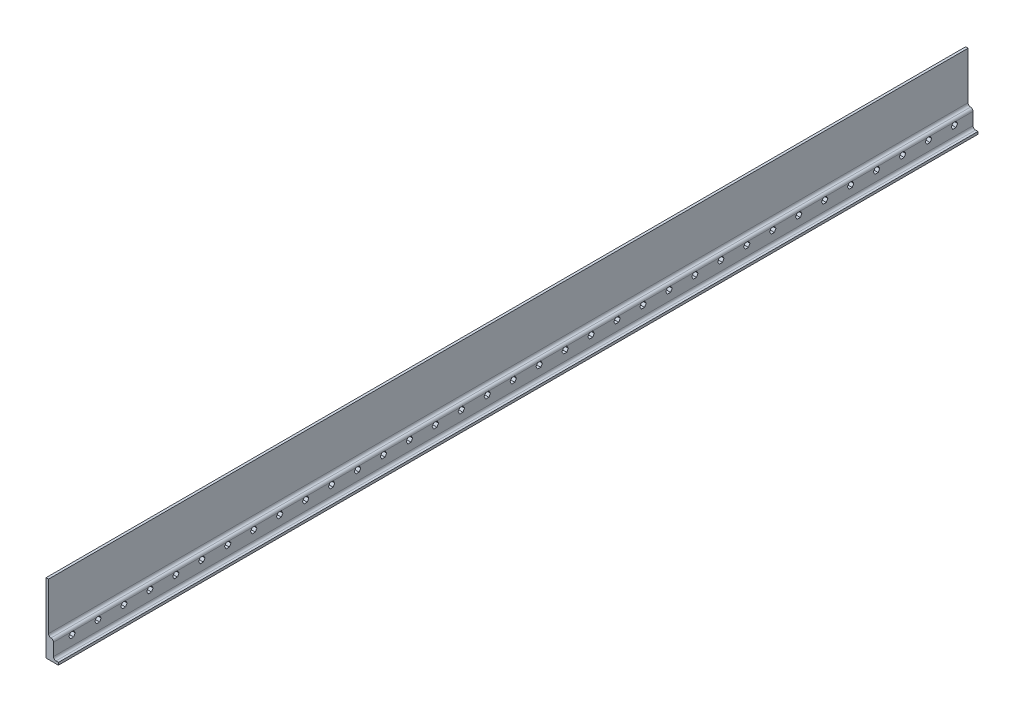
SolidWorks part; units mm, degrees
material "AISI 4340 Steel, annealed"
ref_plane "Front Plane" through (0, 0, 0) normal (0, 0, 1) x (1, 0, 0)
ref_plane "Top Plane" through (0, 0, 0) normal (0, 1, 0) x (1, 0, 0)
ref_plane "Right Plane" through (0, 0, 0) normal (1, 0, 0) x (0, 0, -1)
sketch "Sketch2" plane through (0, 0, 0) normal (0, 0, 1) x (1, 0, 0)
  line L0 (-12.5, 20) -> (12.5, -20) construction
  line L5 (-12.5, -20) -> (12.5, 20) construction
  line L6 (-12.5, 20) -> (-12.5, -20)
  line L7 (-12.5, -20) -> (12.5, -20)
  line L8 (12.5, -20) -> (12.5, -15)
  line L9 (12.5, -15) -> (2.5, -15)
  line L10 (2.5, -15) -> (2.5, 20)
  line L11 (2.5, 20) -> (-12.5, 20)
  point P4 (0, 0)
  point P6 (0, 0)
  dimension "D1" = 25
  dimension "D2" = 40
  dimension "D3" = 15
  dimension "D4" = 5
extrude "General extrude" add sketch "Sketch2" along normal mid plane 1850
fillet "Rounding" radius 5 2 edges at (2.5, 20, 0) (2.5, -15, 0)
sketch "Sketch3" plane through (-12.5, 0, 0) normal (-1, 0, 0) x (0, 0, 1)
  line L1 (-884.3763, 3.8875) -> (-881.1684, 9.4438)
  line L2 (-881.1684, 9.4438) -> (-884.3763, 15)
  line L3 (-884.3763, 15) -> (-890.7921, 15)
  line L4 (-890.7921, 15) -> (-894, 9.4438)
  line L5 (-894, 9.4438) -> (-890.7921, 3.8875)
  line L6 (-890.7921, 3.8875) -> (-884.3763, 3.8875)
  line L7 (-832.1655, 3.8875) -> (-828.9576, 9.4438)
  line L8 (-828.9576, 9.4438) -> (-832.1655, 15)
  line L9 (-832.1655, 15) -> (-838.5813, 15)
  line L10 (-838.5813, 15) -> (-841.7892, 9.4438)
  line L11 (-841.7892, 9.4438) -> (-838.5813, 3.8875)
  line L12 (-838.5813, 3.8875) -> (-832.1655, 3.8875)
  line L13 (-779.9546, 3.8875) -> (-776.7467, 9.4438)
  line L14 (-776.7467, 9.4438) -> (-779.9546, 15)
  line L15 (-779.9546, 15) -> (-786.3704, 15)
  line L16 (-786.3704, 15) -> (-789.5783, 9.4438)
  line L17 (-789.5783, 9.4438) -> (-786.3704, 3.8875)
  line L18 (-786.3704, 3.8875) -> (-779.9546, 3.8875)
  line L19 (-727.7438, 3.8875) -> (-724.5359, 9.4438)
  line L20 (-724.5359, 9.4438) -> (-727.7438, 15)
  line L21 (-727.7438, 15) -> (-734.1596, 15)
  line L22 (-734.1596, 15) -> (-737.3675, 9.4438)
  line L23 (-737.3675, 9.4438) -> (-734.1596, 3.8875)
  line L24 (-734.1596, 3.8875) -> (-727.7438, 3.8875)
  line L25 (-675.533, 3.8875) -> (-672.3251, 9.4438)
  line L26 (-672.3251, 9.4438) -> (-675.533, 15)
  line L27 (-675.533, 15) -> (-681.9488, 15)
  line L28 (-681.9488, 15) -> (-685.1567, 9.4438)
  line L29 (-685.1567, 9.4438) -> (-681.9488, 3.8875)
  line L30 (-681.9488, 3.8875) -> (-675.533, 3.8875)
  line L31 (-623.3221, 3.8875) -> (-620.1142, 9.4438)
  line L32 (-620.1142, 9.4438) -> (-623.3221, 15)
  line L33 (-623.3221, 15) -> (-629.7379, 15)
  line L34 (-629.7379, 15) -> (-632.9458, 9.4438)
  line L35 (-632.9458, 9.4438) -> (-629.7379, 3.8875)
  line L36 (-629.7379, 3.8875) -> (-623.3221, 3.8875)
  line L37 (-571.1113, 3.8875) -> (-567.9034, 9.4438)
  line L38 (-567.9034, 9.4438) -> (-571.1113, 15)
  line L39 (-571.1113, 15) -> (-577.5271, 15)
  line L40 (-577.5271, 15) -> (-580.735, 9.4438)
  line L41 (-580.735, 9.4438) -> (-577.5271, 3.8875)
  line L42 (-577.5271, 3.8875) -> (-571.1113, 3.8875)
  line L43 (-518.9004, 3.8875) -> (-515.6925, 9.4438)
  line L44 (-515.6925, 9.4438) -> (-518.9004, 15)
  line L45 (-518.9004, 15) -> (-525.3163, 15)
  line L46 (-525.3163, 15) -> (-528.5242, 9.4438)
  line L47 (-528.5242, 9.4438) -> (-525.3163, 3.8875)
  line L48 (-525.3163, 3.8875) -> (-518.9004, 3.8875)
  line L49 (-466.6896, 3.8875) -> (-463.4817, 9.4438)
  line L50 (-463.4817, 9.4438) -> (-466.6896, 15)
  line L51 (-466.6896, 15) -> (-473.1054, 15)
  line L52 (-473.1054, 15) -> (-476.3133, 9.4438)
  line L53 (-476.3133, 9.4438) -> (-473.1054, 3.8875)
  line L54 (-473.1054, 3.8875) -> (-466.6896, 3.8875)
  line L55 (-414.4788, 3.8875) -> (-411.2709, 9.4438)
  line L56 (-411.2709, 9.4438) -> (-414.4788, 15)
  line L57 (-414.4788, 15) -> (-420.8946, 15)
  line L58 (-420.8946, 15) -> (-424.1025, 9.4438)
  line L59 (-424.1025, 9.4438) -> (-420.8946, 3.8875)
  line L60 (-420.8946, 3.8875) -> (-414.4788, 3.8875)
  line L61 (-362.2679, 3.8875) -> (-359.06, 9.4438)
  line L62 (-359.06, 9.4438) -> (-362.2679, 15)
  line L63 (-362.2679, 15) -> (-368.6837, 15)
  line L64 (-368.6837, 15) -> (-371.8916, 9.4438)
  line L65 (-371.8916, 9.4438) -> (-368.6837, 3.8875)
  line L66 (-368.6837, 3.8875) -> (-362.2679, 3.8875)
  line L67 (-310.0571, 3.8875) -> (-306.8492, 9.4438)
  line L68 (-306.8492, 9.4438) -> (-310.0571, 15)
  line L69 (-310.0571, 15) -> (-316.4729, 15)
  line L70 (-316.4729, 15) -> (-319.6808, 9.4438)
  line L71 (-319.6808, 9.4438) -> (-316.4729, 3.8875)
  line L72 (-316.4729, 3.8875) -> (-310.0571, 3.8875)
  line L73 (-257.8463, 3.8875) -> (-254.6384, 9.4438)
  line L74 (-254.6384, 9.4438) -> (-257.8463, 15)
  line L75 (-257.8463, 15) -> (-264.2621, 15)
  line L76 (-264.2621, 15) -> (-267.47, 9.4438)
  line L77 (-267.47, 9.4438) -> (-264.2621, 3.8875)
  line L78 (-264.2621, 3.8875) -> (-257.8463, 3.8875)
  line L79 (-205.6354, 3.8875) -> (-202.4275, 9.4438)
  line L80 (-202.4275, 9.4438) -> (-205.6354, 15)
  line L81 (-205.6354, 15) -> (-212.0512, 15)
  line L82 (-212.0512, 15) -> (-215.2591, 9.4438)
  line L83 (-215.2591, 9.4438) -> (-212.0512, 3.8875)
  line L84 (-212.0512, 3.8875) -> (-205.6354, 3.8875)
  line L85 (-153.4246, 3.8875) -> (-150.2167, 9.4438)
  line L86 (-150.2167, 9.4438) -> (-153.4246, 15)
  line L87 (-153.4246, 15) -> (-159.8404, 15)
  line L88 (-159.8404, 15) -> (-163.0483, 9.4438)
  line L89 (-163.0483, 9.4438) -> (-159.8404, 3.8875)
  line L90 (-159.8404, 3.8875) -> (-153.4246, 3.8875)
  line L91 (-101.2138, 3.8875) -> (-98.0059, 9.4438)
  line L92 (-98.0059, 9.4438) -> (-101.2138, 15)
  line L93 (-101.2138, 15) -> (-107.6296, 15)
  line L94 (-107.6296, 15) -> (-110.8375, 9.4438)
  line L95 (-110.8375, 9.4438) -> (-107.6296, 3.8875)
  line L96 (-107.6296, 3.8875) -> (-101.2138, 3.8875)
  line L97 (-49.0029, 3.8875) -> (-45.795, 9.4438)
  line L98 (-45.795, 9.4438) -> (-49.0029, 15)
  line L99 (-49.0029, 15) -> (-55.4187, 15)
  line L100 (-55.4187, 15) -> (-58.6266, 9.4438)
  line L101 (-58.6266, 9.4438) -> (-55.4187, 3.8875)
  line L102 (-55.4187, 3.8875) -> (-49.0029, 3.8875)
  line L103 (3.2079, 3.8875) -> (6.4158, 9.4438)
  line L104 (6.4158, 9.4438) -> (3.2079, 15)
  line L105 (3.2079, 15) -> (-3.2079, 15)
  line L106 (-3.2079, 15) -> (-6.4158, 9.4438)
  line L107 (-6.4158, 9.4438) -> (-3.2079, 3.8875)
  line L108 (-3.2079, 3.8875) -> (3.2079, 3.8875)
  line L109 (55.4187, 3.8875) -> (58.6266, 9.4438)
  line L110 (58.6266, 9.4438) -> (55.4187, 15)
  line L111 (55.4187, 15) -> (49.0029, 15)
  line L112 (49.0029, 15) -> (45.795, 9.4438)
  line L113 (45.795, 9.4438) -> (49.0029, 3.8875)
  line L114 (49.0029, 3.8875) -> (55.4187, 3.8875)
  line L115 (107.6296, 3.8875) -> (110.8375, 9.4438)
  line L116 (110.8375, 9.4438) -> (107.6296, 15)
  line L117 (107.6296, 15) -> (101.2138, 15)
  line L118 (101.2138, 15) -> (98.0059, 9.4438)
  line L119 (98.0059, 9.4438) -> (101.2138, 3.8875)
  line L120 (101.2138, 3.8875) -> (107.6296, 3.8875)
  line L121 (159.8404, 3.8875) -> (163.0483, 9.4438)
  line L122 (163.0483, 9.4438) -> (159.8404, 15)
  line L123 (159.8404, 15) -> (153.4246, 15)
  line L124 (153.4246, 15) -> (150.2167, 9.4438)
  line L125 (150.2167, 9.4438) -> (153.4246, 3.8875)
  line L126 (153.4246, 3.8875) -> (159.8404, 3.8875)
  line L127 (212.0512, 3.8875) -> (215.2591, 9.4438)
  line L128 (215.2591, 9.4438) -> (212.0512, 15)
  line L129 (212.0512, 15) -> (205.6354, 15)
  line L130 (205.6354, 15) -> (202.4275, 9.4438)
  line L131 (202.4275, 9.4438) -> (205.6354, 3.8875)
  line L132 (205.6354, 3.8875) -> (212.0512, 3.8875)
  line L133 (264.2621, 3.8875) -> (267.47, 9.4438)
  line L134 (267.47, 9.4438) -> (264.2621, 15)
  line L135 (264.2621, 15) -> (257.8463, 15)
  line L136 (257.8463, 15) -> (254.6384, 9.4438)
  line L137 (254.6384, 9.4438) -> (257.8463, 3.8875)
  line L138 (257.8463, 3.8875) -> (264.2621, 3.8875)
  line L139 (316.4729, 3.8875) -> (319.6808, 9.4438)
  line L140 (319.6808, 9.4438) -> (316.4729, 15)
  line L141 (316.4729, 15) -> (310.0571, 15)
  line L142 (310.0571, 15) -> (306.8492, 9.4438)
  line L143 (306.8492, 9.4438) -> (310.0571, 3.8875)
  line L144 (310.0571, 3.8875) -> (316.4729, 3.8875)
  line L145 (368.6837, 3.8875) -> (371.8916, 9.4438)
  line L146 (371.8916, 9.4438) -> (368.6837, 15)
  line L147 (368.6837, 15) -> (362.2679, 15)
  line L148 (362.2679, 15) -> (359.06, 9.4438)
  line L149 (359.06, 9.4438) -> (362.2679, 3.8875)
  line L150 (362.2679, 3.8875) -> (368.6837, 3.8875)
  line L151 (420.8946, 3.8875) -> (424.1025, 9.4438)
  line L152 (424.1025, 9.4438) -> (420.8946, 15)
  line L153 (420.8946, 15) -> (414.4788, 15)
  line L154 (414.4788, 15) -> (411.2709, 9.4438)
  line L155 (411.2709, 9.4438) -> (414.4788, 3.8875)
  line L156 (414.4788, 3.8875) -> (420.8946, 3.8875)
  line L157 (473.1054, 3.8875) -> (476.3133, 9.4438)
  line L158 (476.3133, 9.4438) -> (473.1054, 15)
  line L159 (473.1054, 15) -> (466.6896, 15)
  line L160 (466.6896, 15) -> (463.4817, 9.4438)
  line L161 (463.4817, 9.4438) -> (466.6896, 3.8875)
  line L162 (466.6896, 3.8875) -> (473.1054, 3.8875)
  line L163 (525.3163, 3.8875) -> (528.5242, 9.4438)
  line L164 (528.5242, 9.4438) -> (525.3163, 15)
  line L165 (525.3163, 15) -> (518.9004, 15)
  line L166 (518.9004, 15) -> (515.6925, 9.4438)
  line L167 (515.6925, 9.4438) -> (518.9004, 3.8875)
  line L168 (518.9004, 3.8875) -> (525.3163, 3.8875)
  line L169 (577.5271, 3.8875) -> (580.735, 9.4438)
  line L170 (580.735, 9.4438) -> (577.5271, 15)
  line L171 (577.5271, 15) -> (571.1113, 15)
  line L172 (571.1113, 15) -> (567.9034, 9.4438)
  line L173 (567.9034, 9.4438) -> (571.1113, 3.8875)
  line L174 (571.1113, 3.8875) -> (577.5271, 3.8875)
  line L175 (629.7379, 3.8875) -> (632.9458, 9.4438)
  line L176 (632.9458, 9.4438) -> (629.7379, 15)
  line L177 (629.7379, 15) -> (623.3221, 15)
  line L178 (623.3221, 15) -> (620.1142, 9.4438)
  line L179 (620.1142, 9.4438) -> (623.3221, 3.8875)
  line L180 (623.3221, 3.8875) -> (629.7379, 3.8875)
  line L181 (681.9488, 3.8875) -> (685.1567, 9.4438)
  line L182 (685.1567, 9.4438) -> (681.9488, 15)
  line L183 (681.9488, 15) -> (675.533, 15)
  line L184 (675.533, 15) -> (672.3251, 9.4438)
  line L185 (672.3251, 9.4438) -> (675.533, 3.8875)
  line L186 (675.533, 3.8875) -> (681.9488, 3.8875)
  line L187 (734.1596, 3.8875) -> (737.3675, 9.4438)
  line L188 (737.3675, 9.4438) -> (734.1596, 15)
  line L189 (734.1596, 15) -> (727.7438, 15)
  line L190 (727.7438, 15) -> (724.5359, 9.4438)
  line L191 (724.5359, 9.4438) -> (727.7438, 3.8875)
  line L192 (727.7438, 3.8875) -> (734.1596, 3.8875)
  line L193 (786.3704, 3.8875) -> (789.5783, 9.4438)
  line L194 (789.5783, 9.4438) -> (786.3704, 15)
  line L195 (786.3704, 15) -> (779.9546, 15)
  line L196 (779.9546, 15) -> (776.7467, 9.4438)
  line L197 (776.7467, 9.4438) -> (779.9546, 3.8875)
  line L198 (779.9546, 3.8875) -> (786.3704, 3.8875)
  line L199 (838.5813, 3.8875) -> (841.7892, 9.4438)
  line L200 (841.7892, 9.4438) -> (838.5813, 15)
  line L201 (838.5813, 15) -> (832.1655, 15)
  line L202 (832.1655, 15) -> (828.9576, 9.4438)
  line L203 (828.9576, 9.4438) -> (832.1655, 3.8875)
  line L204 (832.1655, 3.8875) -> (838.5813, 3.8875)
  line L205 (890.7921, 3.8875) -> (894, 9.4438)
  line L206 (894, 9.4438) -> (890.7921, 15)
  line L207 (890.7921, 15) -> (884.3763, 15)
  line L208 (884.3763, 15) -> (881.1684, 9.4438)
  line L209 (881.1684, 9.4438) -> (884.3763, 3.8875)
  line L210 (884.3763, 3.8875) -> (890.7921, 3.8875)
  line L212 (925, 20) -> (925, -20) construction
  line L213 (-925, 20) -> (-925, -20) construction
  line L215 (925, 20) -> (-925, 20) construction
  circle A0 centre (-887.5842, 9.4438) radius 5.5563 construction
  circle A1 centre (-835.3734, 9.4438) radius 5.5563 construction
  point P10 (0, 0)
  point P11 (0, 0)
  point P222 (-835.3734, 15)
  dimension "D1" = 11.1125
  dimension "D2" = 5
  dimension "D4" = 31
  dimension "D5" = 31
  dimension "D3" = 35
extrude "Roller holders" cut sketch "Sketch3" against normal through all
sketch "Sketch5" plane through (0, 20, 0) normal (0, 1, 0) x (1, 0, 0)
  line L0 (-2.5, -925) -> (-12.5, -925) construction
  line L1 (-12.5, 925) -> (-7.5, 925)
  line L2 (-12.5, 925) -> (-12.5, -925)
  line L3 (-12.5, -925) -> (-7.5, -925)
  line L4 (-7.5, 925) -> (-7.5, -925)
  dimension "D1" = 5
extrude "Guard rail" add sketch "Sketch5" along normal blind 100
fillet "Guard rail support fillet" radius 5 1 edges at (-7.5, 20, 0)
